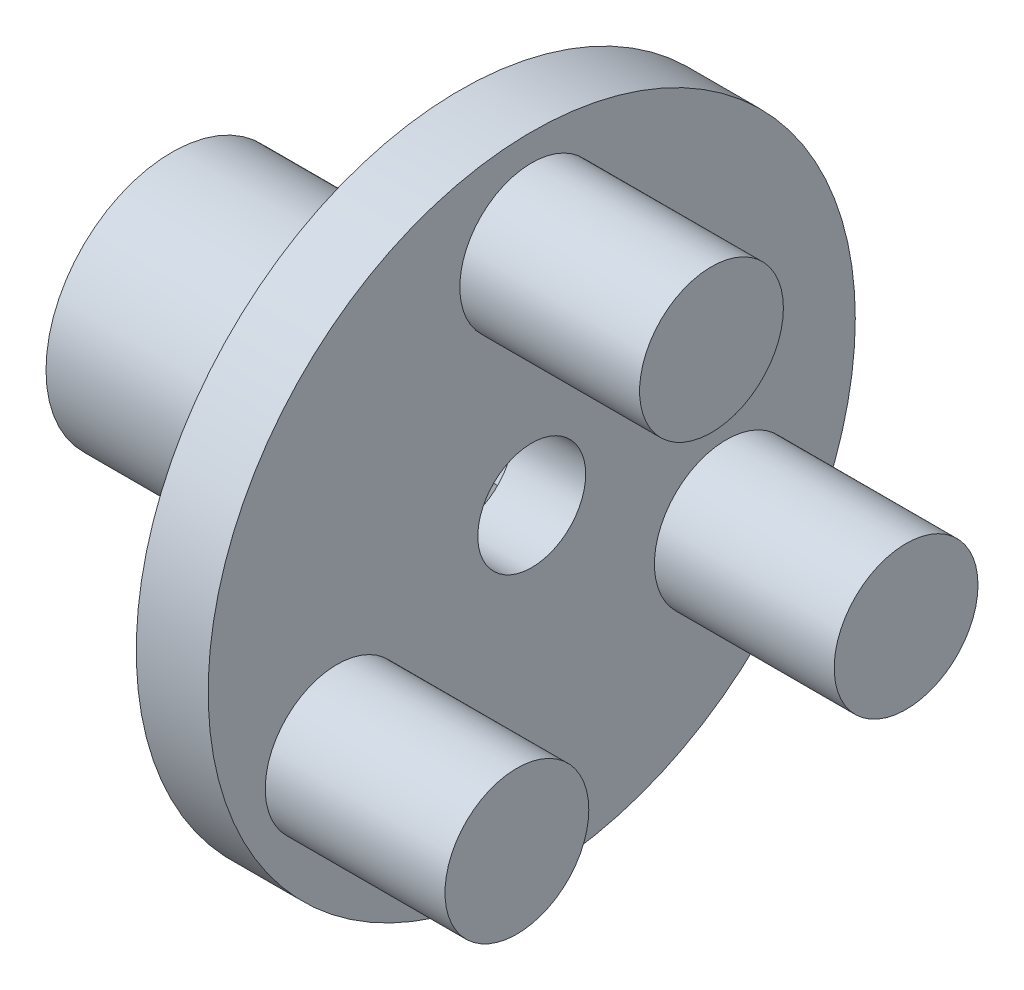
SolidWorks part; units mm, degrees
ref_plane "前视基准面" through (0, 0, 0) normal (0, 0, 1) x (1, 0, 0)
ref_plane "上视基准面" through (0, 0, 0) normal (0, 1, 0) x (1, 0, 0)
ref_plane "右视基准面" through (0, 0, 0) normal (1, 0, 0) x (0, 0, -1)
other "Configuration Table"
sketch "草图1" plane through (0, 0, 0) normal (1, 0, 0) x (0, 0, -1)
  circle A0 centre (0, 0) radius 9
  circle A1 centre (0, 6.25) radius 2
  circle A2 centre (5.4127, -3.125) radius 2
  circle A3 centre (-5.4127, -3.125) radius 2
  point P12 (0, 0)
  dimension "D2" = 4
  dimension "D3" = 18
  dimension "D1" = 6.25
  dimension "D4" = 3
extrude "凸台-拉伸1" add sketch "草图1" along normal blind 2 contours A0
extrude "凸台-拉伸2" add sketch "草图1<3>" along normal blind 5 from surface contours A1 | A3 | A2 region at (0, 6.25, 0) region at (0, -3.125, -5.4127) region at (0, -3.125, 5.4127) starting at face at (2, 0, -9)
sketch "草图1<3>" plane through (0, 0, 0) normal (1, 0, 0) x (0, 0, -1) same geometry as "草图1"
sketch "草图2" plane through (0, 0, 0) normal (-1, 0, 0) x (0, 0, 1)
  circle A0 centre (0, 0) radius 1.5
  circle A1 centre (0, 0) radius 5
  dimension "D1" = 3
  dimension "D2" = 10
extrude "凸台-拉伸3" add sketch "草图2" along normal blind 0.01
sketch "草图3" plane through (-0.01, 0, 0) normal (-1, 0, 0) x (0, 0, 1)
  line L1 (-2.3043, -1.2043) -> (2.3043, -1.2043)
  line L2 (-2.3043, -1.2043) -> (-2.3043, 1.2043)
  line L3 (-2.3043, 1.2043) -> (2.3043, 1.2043)
  line L4 (2.3043, -1.2043) -> (2.3043, 1.2043)
  line L5 (-2.3043, -1.2043) -> (2.3043, 1.2043) construction
  line L6 (-2.3043, 1.2043) -> (2.3043, -1.2043) construction
  line L7 (-1.2043, -2.3043) -> (1.2043, -2.3043)
  line L8 (-1.2043, -2.3043) -> (-1.2043, 2.3043)
  line L9 (-1.2043, 2.3043) -> (1.2043, 2.3043)
  line L10 (1.2043, -2.3043) -> (1.2043, 2.3043)
  line L11 (-1.2043, -2.3043) -> (1.2043, 2.3043) construction
  line L12 (-1.2043, 2.3043) -> (1.2043, -2.3043) construction
  circle A0 centre (0, 0) radius 2.6
  circle A1 centre (0, 0) radius 3.5
  dimension "D1" = 7
  dimension "D2" = 5.2
  dimension "D3" = 1.1
extrude "凸台-拉伸4" add sketch "草图3" along normal blind 8 contours A1 A0 | L8 A0 L3 | L1 A0 L8 | L10 A0 L1 | L3 A0 L10 region at (-0.01, -1.6079, -1.6079) region at (-0.01, 1.6079, -1.6079) region at (-0.01, -1.6079, 1.6079) region at (-0.01, 1.6079, 1.6079) region at (-0.01, 0, -3.401)
extrude "切除-拉伸1" cut sketch "草图2<5>" against normal up to next contours A0 region at (0, 0, 0)
sketch "草图2<5>" plane through (0, 0, 0) normal (-1, 0, 0) x (0, 0, 1) same geometry as "草图2"
